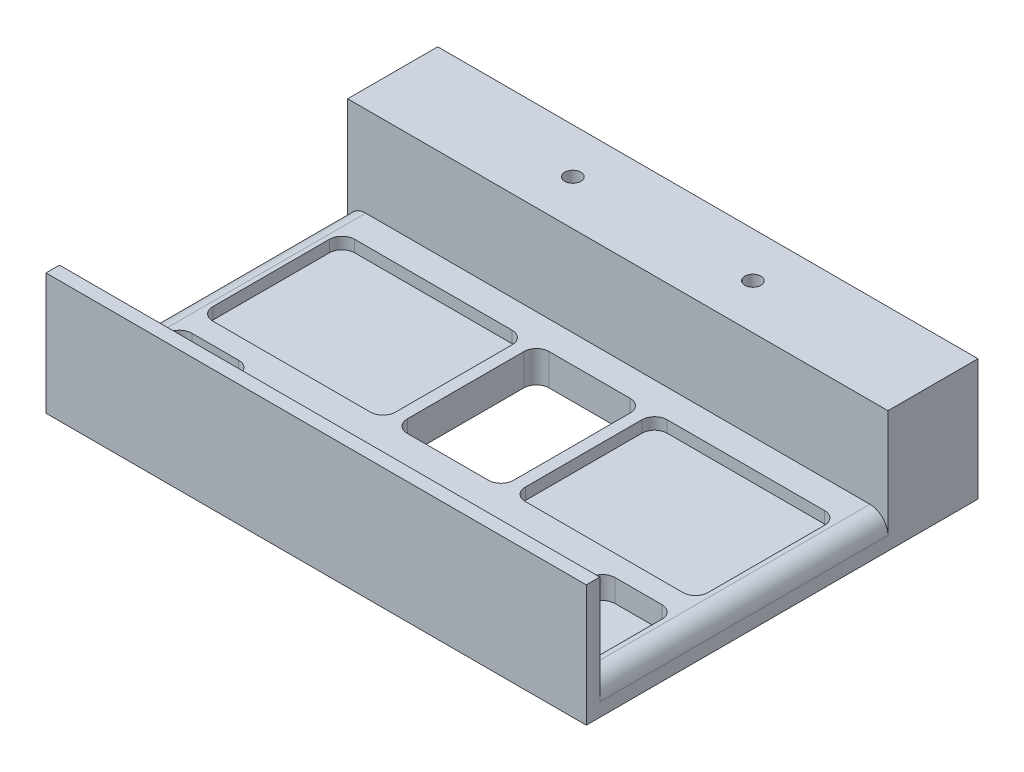
SolidWorks part; units mm, degrees
material "1345 Alloy"
ref_plane "Front Plane" through (0, 0, 0) normal (0, 0, 1) x (1, 0, 0)
ref_plane "Top Plane" through (0, 0, 0) normal (0, 1, 0) x (1, 0, 0)
ref_plane "Right Plane" through (0, 0, 0) normal (1, 0, 0) x (0, 0, -1)
sketch "Sketch1" plane through (0, 0, 0) normal (0, 1, 0) x (1, 0, 0)
  line L1 (-38.1, 22.225) -> (38.1, 22.225)
  line L2 (-38.1, 22.225) -> (-38.1, -22.225)
  line L3 (-38.1, -22.225) -> (38.1, -22.225)
  line L4 (38.1, 22.225) -> (38.1, -22.225)
  line L5 (-38.1, 22.225) -> (38.1, -22.225) construction
  line L6 (-38.1, -22.225) -> (38.1, 22.225) construction
  point P0 (0, 0)
  dimension "D1" = 44.45
  dimension "D2" = 76.2
extrude "Boss-Extrude1" add sketch "Sketch1" along normal blind 4.445
sketch "Sketch2" plane through (0, 4.445, 0) normal (0, 1, 0) x (1, 0, 0)
  line L0 (38.1, -22.225) -> (38.1, 22.225) construction
  line L1 (-38.1, 22.225) -> (38.1, 22.225)
  line L2 (-38.1, 22.225) -> (-38.1, 20.32)
  line L3 (-38.1, 20.32) -> (38.1, 20.32)
  line L4 (38.1, 22.225) -> (38.1, 20.32)
  line L5 (-38.1, 0) -> (38.1, 0) construction
  line L6 (-38.1, 22.225) -> (-38.1, -22.225) construction
  line L7 (38.1, -22.225) -> (38.1, -20.32)
  line L8 (-38.1, -20.32) -> (38.1, -20.32)
  line L9 (-38.1, -22.225) -> (-38.1, -20.32)
  line L10 (-38.1, -22.225) -> (38.1, -22.225)
  dimension "D1" = 1.905
extrude "Boss-Extrude2" add sketch "Sketch2" along normal blind 12.7
sketch "Sketch6" plane through (0, 4.445, 0) normal (0, 1, 0) x (1, 0, 0)
  line L0 (-38.1, 20.32) -> (-38.1, -20.32) construction
  line L1 (38.1, -20.32) -> (38.1, 20.32) construction
  line L2 (-38.1, 20.32) -> (38.1, 20.32) construction
  line L3 (-7.5, 16.35) -> (7.5, 16.35) construction
  line L4 (-7.5, 16.35) -> (-7.5, -3.65) construction
  line L5 (-7.5, -3.65) -> (7.5, -3.65) construction
  line L6 (7.5, 16.35) -> (7.5, -3.65) construction
  line L7 (-38.1, 6.35) -> (38.1, 6.35) construction
  line L8 (-7.5, 16.35) -> (7.5, -3.65) construction
  line L9 (-7.5, -3.65) -> (7.5, 16.35) construction
  line L10 (-38.1, -7.62) -> (38.1, -7.62) construction
  line L11 (-5.722, -1.872) -> (5.722, 14.572) construction
  line L12 (-7.5, 14.572) -> (-7.5, -1.872)
  line L13 (-5.722, -3.65) -> (5.722, -3.65)
  line L14 (7.5, 14.572) -> (7.5, -1.872)
  line L15 (-5.722, 16.35) -> (5.722, 16.35)
  line L16 (38.1, 20.32) -> (38.1, -7.62) construction
  line L17 (-38.1, 20.32) -> (-38.1, -7.62) construction
  line L18 (-5.722, 14.572) -> (5.722, -1.872) construction
  arc A0 (-5.722, -3.65) -> (-7.5, -1.872) centre (-5.722, -1.872) cw
  arc A1 (5.722, -3.65) -> (7.5, -1.872) centre (5.722, -1.872) ccw
  arc A2 (7.5, 14.572) -> (5.722, 16.35) centre (5.722, 14.572) ccw
  arc A3 (-5.722, 16.35) -> (-7.5, 14.572) centre (-5.722, 14.572) ccw
  point P0 (0, 6.35)
  point P16 (0, 6.35)
  dimension "D4" = 1.778
  dimension "D1" = 15
  dimension "D2" = 20
  dimension "D3" = 27.94
extrude "Cut-Extrude3" cut sketch "Sketch6" against normal through all
sketch "Sketch7" plane through (0, 4.445, 0) normal (0, 1, 0) x (1, 0, 0)
  line L0 (0, 6.35) -> (-38.1, 6.35) construction
  line L1 (-38.1, 20.32) -> (-38.1, -20.32) construction
  line L2 (-34.925, 16.35) -> (-9.151, 16.35)
  line L3 (-34.925, 16.35) -> (-34.925, -3.65)
  line L4 (-34.925, -3.65) -> (-9.151, -3.65)
  line L7 (0, 16.35) -> (0, -3.65) construction
  line L8 (-9.151, 16.35) -> (-9.151, -3.65)
  line L10 (5.722, 16.35) -> (-5.722, 16.35) construction
  line L11 (-5.722, -3.65) -> (5.722, -3.65) construction
  line L12 (-7.5, 14.572) -> (-7.5, -1.872) construction
  line L13 (9.151, 16.35) -> (9.151, -3.65)
  line L14 (34.925, 16.35) -> (9.151, 16.35)
  line L16 (34.925, -3.65) -> (9.151, -3.65)
  line L17 (34.925, 16.35) -> (34.925, -3.65)
  dimension "D1" = 3.175
  dimension "D2" = 1.651
extrude "Cut-Extrude4" cut sketch "Sketch7" against normal blind 1.651
sketch "Sketch11" plane through (0, 4.445, 0) normal (0, 1, 0) x (1, 0, 0)
  line L0 (0, 0) -> (0, -20.32) construction
  line L1 (-34.925, -6.604) -> (-34.925, -18.796)
  line L2 (-38.1, 20.32) -> (-38.1, -20.32) construction
  line L3 (38.1, -20.32) -> (-38.1, -20.32) construction
  line L6 (-34.925, -18.796) -> (-24.765, -18.796)
  line L7 (-24.765, -18.796) -> (-24.765, -6.604)
  line L8 (-24.765, -6.604) -> (-34.925, -6.604)
  line L9 (-38.1, -22.225) -> (38.1, -22.225) construction
  line L10 (24.765, -6.604) -> (34.925, -6.604)
  line L11 (24.765, -18.796) -> (24.765, -6.604)
  line L12 (34.925, -18.796) -> (24.765, -18.796)
  line L13 (34.925, -6.604) -> (34.925, -18.796)
  dimension "D1" = 3.175
  dimension "D2" = 12.192
  dimension "D3" = 10.16
  dimension "D4" = 3.429
extrude "Cut-Extrude6" cut sketch "Sketch11" against normal blind 3.175
sketch "Sketch13" plane through (0, 0, -20.32) normal (0, 0, 1) x (1, 0, 0)
  line L4 (-38.1, 0) -> (38.1, 0)
  line L5 (-38.1, 17.145) -> (-38.1, 0)
  line L6 (38.1, 17.145) -> (-38.1, 17.145)
  line L7 (38.1, 0) -> (38.1, 17.145)
  line L8 (-38.1, 0) -> (38.1, 0)
  line L9 (-38.1, 17.145) -> (-38.1, 0)
  line L10 (38.1, 17.145) -> (-38.1, 17.145)
  line L11 (38.1, 0) -> (38.1, 17.145)
  dimension "D1" = 0
extrude "Boss-Extrude3" add sketch "Sketch13" against normal blind 12.7
sketch3d "3DSketch1"
  line L0 (-29.845, 4.445, 18.796) -> (-29.845, 4.445, 20.32) construction
  line L1 (-34.925, 4.445, 18.796) -> (-24.765, 4.445, 18.796) construction
  line L2 (38.1, 4.445, 20.32) -> (-38.1, 4.445, 20.32) construction
  line L3 (-29.845, 4.445, 20.32) -> (-29.845, 17.145, 20.32) construction
  line L4 (38.1, 17.145, 20.32) -> (-38.1, 17.145, 20.32) construction
fillet "Fillet1" radius 1.778 16 edges at (-34.925, 2.8575, 6.604) (-24.765, 2.8575, 6.604) (24.765, 2.8575, 18.796) (34.925, 2.8575, 18.796) (24.765, 2.8575, 6.604) (34.925, 2.8575, 6.604) (-34.925, 2.8575, 18.796) (-24.765, 2.8575, 18.796) (-9.151, 3.6195, 3.65) (-9.151, 3.6195, -16.35) (9.151, 3.6195, -16.35) (9.151, 3.6195, 3.65) (34.925, 3.6195, 3.65) (34.925, 3.6195, -16.35) (-34.925, 3.6195, 3.65) (-34.925, 3.6195, -16.35)
hole_wizard "#10-32 Tapped Hole1" positions "Sketch16" profile "Sketch15" tap size "#10-32" standard "Ansi Inch"
sketch "Sketch16" plane through (0, 0, -33.02) normal (0, 0, -1) x (-1, 0, 0)
  line L0 (0, 0) -> (0, 17.145) construction
  line L1 (38.1, 0) -> (-38.1, 0) construction
  line L2 (-38.1, 17.145) -> (38.1, 17.145) construction
  line L5 (-38.1, 0) -> (-38.1, 17.145) construction
  point P0 (-25.4, 8.89)
  point P16 (25.4, 8.89)
  dimension "D1" = 12.7
  dimension "D2" = 8.89
sketch "Sketch15" plane through (25.4, 8.89, -33.02) normal (1, 0, 0) x (0, 1, 0)
  line L0 (0, 0) -> (0, 7.5633)
  line L1 (0, 7.5633) -> (2.0193, 6.35)
  line L2 (2.0193, 6.35) -> (2.0193, 0)
  line L5 (2.0193, 0) -> (0, 0)
  line L10 (0, 7.5633) -> (-2.0193, 6.35) construction
  line L11 (0, -6.35) -> (0, 107.95) construction
  dimension "Tap Drill Dia." = 4.0386
  dimension "Tap Drill Depth" = 6.35
  dimension "Drill Angle" = 118
cosmetic thread "Hole Thread1" parameters "D1"=6.35, "D2"=4.826
cosmetic thread "Hole Thread2" parameters "D1"=6.35, "D2"=4.826
hole_wizard "#4-40 Tapped Hole1" positions "Sketch18" profile "Sketch17" tap size "#4-40" standard "Ansi Inch"
sketch "Sketch18" plane through (0, 17.145, 0) normal (0, 1, 0) x (-1, 0, 0)
  point P6 (12.7, -26.67)
  point P10 (-12.7, -26.67)
sketch "Sketch17" plane through (-12.7, 17.145, -26.67) normal (1, 0, 0) x (0, 0, 1)
  line L0 (0, 0) -> (0, 7.0292)
  line L1 (0, 7.0292) -> (1.1303, 6.35)
  line L2 (1.1303, 6.35) -> (1.1303, 0)
  line L5 (1.1303, 0) -> (0, 0)
  line L10 (0, 7.0292) -> (-1.1303, 6.35) construction
  line L11 (0, -6.35) -> (0, 107.95) construction
  dimension "Tap Drill Dia." = 2.2606
  dimension "Tap Drill Depth" = 6.35
  dimension "Drill Angle" = 118
cosmetic thread "Hole Thread3" parameters "D1"=6.35, "D2"=2.8448
cosmetic thread "Hole Thread4" parameters "D1"=6.35, "D2"=2.8448
sketch "refSketch" plane through (0, 4.445, 0) normal (0, 1, 0) x (1, 0, 0)
  line L0 (-5.722, 14.572) -> (5.722, -1.872) construction
  line L1 (-5.722, -1.872) -> (5.722, 14.572) construction
  point P8 (0, 6.35)
ref_axis "Axis1" through (0, -44.4835, -6.35) along (0, 1, 0)
fillet "Fillet2" radius 2.54 2 edges
